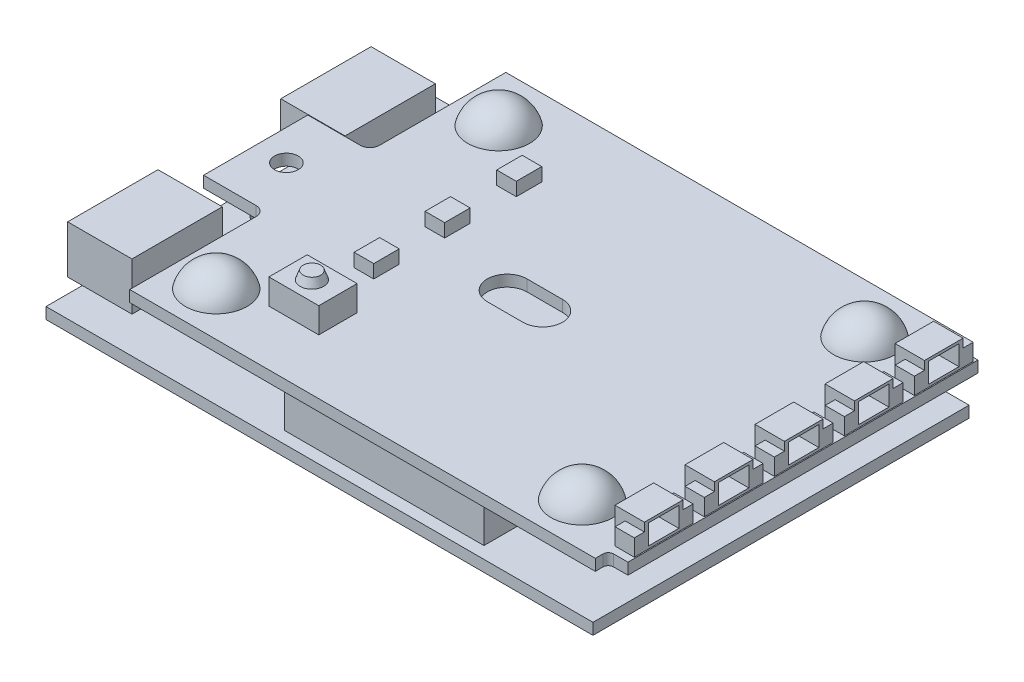
SolidWorks part; units mm, degrees
ref_plane "Front Plane" through (0, 0, 0) normal (0, 0, 1) x (1, 0, 0)
ref_plane "Top Plane" through (0, 0, 0) normal (0, 1, 0) x (1, 0, 0)
ref_plane "Right Plane" through (0, 0, 0) normal (1, 0, 0) x (0, 0, -1)
sketch "Sketch1" plane through (0, 0, 0) normal (0, 1, 0) x (1, 0, 0)
  line L1 (0, 0) -> (77.978, 0)
  line L2 (0, 0) -> (0, -53.6194)
  line L3 (0, -53.6194) -> (77.978, -53.6194)
  line L4 (77.978, 0) -> (77.978, -53.6194)
  dimension "D1" = 77.978
  dimension "D2" = 53.6194
extrude "Bottom Board" add sketch "Sketch1" along normal blind 1.6129
sketch "Sketch2" plane through (0, 1.6129, 0) normal (0, 1, 0) x (-1, 0, 0)
  line L0 (0, 0) -> (0, 53.6194) construction
  line L1 (2.0955, 5.1816) -> (-7.0739, 5.1816)
  line L2 (2.0955, 5.1816) -> (2.0955, 18.0594)
  line L3 (2.0955, 18.0594) -> (-7.0739, 18.0594)
  line L4 (-7.0739, 5.1816) -> (-7.0739, 18.0594)
  line L5 (-77.978, 0) -> (0, 0) construction
  dimension "D1" = 12.8778
  dimension "D2" = 9.1694
  dimension "D3" = 5.1816
  dimension "D4" = 2.0955
extrude "Connector Body" add sketch "Sketch2" along normal blind 6.8199
sketch "Sketch4" plane through (-2.0955, 0, 0) normal (-1, 0, 0) x (0, 0, 1)
  line L0 (5.1816, 8.4328) -> (5.1816, 1.6129) construction
  line L1 (5.7658, 7.8105) -> (8.3947, 7.8105)
  line L2 (5.7658, 7.8105) -> (5.7658, 5.2197)
  line L3 (5.7658, 5.2197) -> (8.3947, 5.2197)
  line L4 (8.3947, 7.8105) -> (8.3947, 5.2197)
  line L5 (5.1816, 8.4328) -> (18.0594, 8.4328) construction
  line L6 (8.7926, 7.8105) -> (8.7926, 5.2197)
  line L7 (8.7926, 5.2197) -> (11.4215, 5.2197)
  line L8 (11.4215, 7.8105) -> (11.4215, 5.2197)
  line L9 (8.7926, 7.8105) -> (11.4215, 7.8105)
  line L10 (11.8195, 7.8105) -> (11.8195, 5.2197)
  line L11 (11.8195, 5.2197) -> (14.4484, 5.2197)
  line L12 (14.4484, 7.8105) -> (14.4484, 5.2197)
  line L13 (11.8195, 7.8105) -> (14.4484, 7.8105)
  line L14 (14.8463, 7.8105) -> (14.8463, 5.2197)
  line L15 (14.8463, 5.2197) -> (17.4752, 5.2197)
  line L16 (17.4752, 7.8105) -> (17.4752, 5.2197)
  line L17 (14.8463, 7.8105) -> (17.4752, 7.8105)
  line L18 (5.7658, 4.826) -> (5.7658, 2.2352)
  line L19 (5.7658, 2.2352) -> (8.3947, 2.2352)
  line L20 (8.3947, 4.826) -> (8.3947, 2.2352)
  line L21 (5.7658, 4.826) -> (8.3947, 4.826)
  line L22 (8.7926, 4.826) -> (8.7926, 2.2352)
  line L23 (8.7926, 2.2352) -> (11.4215, 2.2352)
  line L24 (11.4215, 4.826) -> (11.4215, 2.2352)
  line L25 (8.7926, 4.826) -> (11.4215, 4.826)
  line L26 (11.8195, 4.826) -> (11.8195, 2.2352)
  line L27 (11.8195, 2.2352) -> (14.4484, 2.2352)
  line L28 (14.4484, 4.826) -> (14.4484, 2.2352)
  line L29 (11.8195, 4.826) -> (14.4484, 4.826)
  line L30 (14.8463, 4.826) -> (14.8463, 2.2352)
  line L31 (14.8463, 2.2352) -> (17.4752, 2.2352)
  line L32 (17.4752, 4.826) -> (17.4752, 2.2352)
  line L33 (14.8463, 4.826) -> (17.4752, 4.826)
  line L34 (18.0594, 8.4328) -> (18.0594, 1.6129) construction
  line L35 (17.4752, 7.4085) -> (18.0594, 7.4085) construction
  line L36 (5.7658, 7.5345) -> (5.1816, 7.5345) construction
  line L37 (7.8077, 7.8105) -> (7.8077, 8.4328)
  line L38 (7.8077, 2.2352) -> (7.8077, 1.6129)
  line L39 (5.1816, 1.6129) -> (18.0594, 1.6129) construction
  dimension "D1" = 2.6289
  dimension "D2" = 2.5908
  dimension "D3" = 0.5842
  dimension "D4" = 0.6223
  dimension "D5" = 4
  dimension "D6" = 2
extrude "Connector Holes" cut sketch "Sketch4" against normal blind 5.08 contours L4 L1 L2 L3 | L9 L6 L7 L8 | L13 L10 L11 L12 | L17 L14 L15 L16 | L33 L30 L31 L32 | L29 L26 L27 L28 | L25 L22 L23 L24 | L21 L18 L19 L20 region at (-2.0955, 6.5151, 7.0802) region at (-2.0955, 6.5151, 10.1071) region at (-2.0955, 6.5151, 13.1339) region at (-2.0955, 6.5151, 16.1608) region at (-2.0955, 3.5306, 7.0802) region at (-2.0955, 3.5306, 10.1071) region at (-2.0955, 3.5306, 13.1339) region at (-2.0955, 3.5306, 16.1608)
ref_plane "Center Plane" through (0, 0, 26.8097) normal (0, 0, -1) x (-1, 0, 0)
mirror "Connector Mirror" about plane through (0, 0, 26.8097) normal (0, 0, -1) of "Connector Holes", "Connector Body"
sketch "Sketch5" plane through (0, 1.6129, 0) normal (0, 1, 0) x (1, 0, 0)
  line L0 (77.978, -26.8097) -> (0, -26.8097) construction
  line L1 (77.978, -53.6194) -> (77.978, 0) construction
  line L2 (0, -18.0594) -> (0, -35.56) construction
  line L3 (2.9845, -26.8097) -> (2.9845, -21.4955) construction
  line L4 (36.0172, -26.8097) -> (36.0172, -8.1241) construction
  line L5 (0, -18.0594) -> (0, -35.56) construction
  circle A0 centre (4.68, -26.8097) radius 1.6955
  circle A1 centre (39.0652, -26.8097) radius 3.048
  dimension "D1" = 3.3909
  dimension "D3" = 6.096
  dimension "D2" = 2.9845
  dimension "D4" = 36.0172
extrude "Bottom Board Hole" cut sketch "Sketch5" against normal up to next
sketch "Sketch6" plane through (0, 1.6129, 0) normal (0, 1, 0) x (-1, 0, 0)
  line L0 (-77.978, 0) -> (0, 0) construction
  line L1 (-39.37, 1.7018) -> (-67.818, 1.7018)
  line L2 (-39.37, 1.7018) -> (-39.37, 7.2644)
  line L3 (-39.37, 7.2644) -> (-67.818, 7.2644)
  line L4 (-67.818, 1.7018) -> (-67.818, 7.2644)
  line L5 (-77.978, 53.6194) -> (-77.978, 0) construction
  line L6 (-32.2834, 46.355) -> (-60.7314, 46.355)
  line L7 (-32.2834, 46.355) -> (-32.2834, 51.9176)
  line L8 (-32.2834, 51.9176) -> (-60.7314, 51.9176)
  line L9 (-60.7314, 46.355) -> (-60.7314, 51.9176)
  line L10 (0, 18.0594) -> (0, 35.56) construction
  line L12 (-44.4047, 1.7018) -> (-44.4047, 0) construction
  line L13 (-37.561, 51.9176) -> (-37.561, 53.6194) construction
  line L14 (0, 53.6194) -> (-77.978, 53.6194) construction
  dimension "D1" = 28.448
  dimension "D2" = 5.5626
  dimension "D3" = 1.7018
  dimension "D4" = 10.16
  dimension "D5" = 28.448
  dimension "D6" = 5.5626
  dimension "D7" = 32.2834
extrude "Layer Connectors" add sketch "Sketch6" along normal blind 6.4516
sketch "Sketch7" plane through (0, 8.0645, 0) normal (0, 1, 0) x (1, 0, 0)
  line L0 (77.978, -53.6194) -> (77.978, 0) construction
  line L1 (78.3082, 0) -> (11.938, 0)
  line L2 (81.1022, -1.8542) -> (81.1022, -51.7652)
  line L3 (78.3082, -53.6194) -> (11.938, -53.6194)
  line L4 (11.938, 0) -> (11.938, -18.0086)
  line L5 (0, -18.0594) -> (0, -35.56) construction
  line L6 (77.978, 0) -> (0, 0) construction
  line L7 (0, -53.6194) -> (77.978, -53.6194) construction
  line L8 (15.6034, 0) -> (15.6034, -19.3802) construction
  line L9 (10.5664, -19.3802) -> (3.0861, -19.3802)
  line L10 (11.938, -35.6108) -> (11.938, -53.6194)
  line L11 (10.5664, -34.2392) -> (3.0861, -34.2392)
  line L12 (3.0861, -19.3802) -> (3.0861, -34.2392)
  line L13 (10.5664, -19.3802) -> (15.6034, -19.3802) construction
  line L14 (16.8171, -34.2392) -> (16.8171, -53.6194) construction
  line L15 (10.5664, -34.2392) -> (16.8171, -34.2392) construction
  line L16 (77.978, -26.8097) -> (0, -26.8097) construction
  line L17 (5.7658, -26.8097) -> (5.7658, -22.9762) construction
  line L18 (36.1061, -26.8097) -> (46.8249, -26.8097) construction
  line L19 (38.9318, -23.984) -> (43.9992, -23.984)
  line L20 (36.1061, -26.8097) -> (36.1061, -33.1542) construction
  line L21 (38.9318, -29.6354) -> (43.9992, -29.6355)
  line L22 (78.3082, -53.6194) -> (78.3082, -52.5272)
  line L23 (81.1022, -51.7652) -> (79.0702, -51.7652)
  line L25 (81.1022, -1.8542) -> (79.0702, -1.8542)
  line L26 (78.3082, 0) -> (78.3082, -1.0922)
  arc A0 (11.938, -18.0086) -> (10.5664, -19.3802) centre (10.5664, -18.0086) cw
  arc A1 (10.5664, -34.2392) -> (11.938, -35.6108) centre (10.5664, -35.6108) cw
  circle A2 centre (7.4613, -26.8097) radius 1.6955
  circle A3 centre (4.68, -26.8097) radius 1.6955 construction
  arc A4 (38.9318, -29.6354) -> (38.9318, -23.984) centre (38.9318, -26.8097) cw
  arc A5 (43.9992, -23.984) -> (43.9992, -29.6355) centre (43.9992, -26.8097) cw
  arc A6 (79.0702, -1.8542) -> (78.3082, -1.0922) centre (79.0702, -1.0922) cw
  arc A7 (79.0702, -51.7652) -> (78.3082, -52.5272) centre (79.0702, -52.5272) ccw
  point P45 (78.3082, -1.8542)
  dimension "D5" = 1.3716
  dimension "D6" = 1.3716
  dimension "D13" = 0.762
  dimension "D1" = 3.1242
  dimension "D2" = 11.938
  dimension "D3" = 19.3802
  dimension "D4" = 3.0861
  dimension "D7" = 2.6797
  dimension "D8" = 5.6515
  dimension "D9" = 10.7188
  dimension "D10" = 33.02
  dimension "D11" = 2.794
  dimension "D12" = 1.8542
extrude "Top Board" add sketch "Sketch7" along normal blind 1.6129
sketch "Sketch8" plane through (0, 9.6774, 0) normal (0, 1, 0) x (1, 0, 0)
  line L1 (80.9498, -2.3876) -> (78.2066, -2.3876)
  line L2 (80.9498, -2.3876) -> (80.9498, -10.7696)
  line L3 (80.9498, -10.7696) -> (78.2066, -10.7696)
  line L4 (78.2066, -2.3876) -> (78.2066, -10.7696)
  line L5 (78.3082, 0) -> (11.938, 0) construction
  line L6 (81.1022, -51.7652) -> (81.1022, -1.8542) construction
  dimension "D1" = 2.7432
  dimension "D2" = 8.382
  dimension "D3" = 2.3876
  dimension "D4" = 0.1524
extrude "Maker Connector Sides" add sketch "Sketch8" along normal blind 2.3876
sketch "Sketch9" plane through (0, 12.065, 0) normal (0, 1, 0) x (1, 0, 0)
  line L0 (80.9498, -10.7696) -> (80.9498, -2.3876) construction
  line L1 (80.9498, -3.8227) -> (76.7588, -3.8227)
  line L2 (80.9498, -3.8227) -> (80.9498, -9.3345)
  line L3 (80.9498, -9.3345) -> (76.7588, -9.3345)
  line L4 (76.7588, -3.8227) -> (76.7588, -9.3345)
  line L6 (78.7411, -2.3876) -> (78.7411, -3.8227) construction
  line L7 (80.9498, -2.3876) -> (78.2066, -2.3876) construction
  line L9 (78.7411, -9.3345) -> (78.7411, -10.7696) construction
  line L10 (78.2066, -10.7696) -> (80.9498, -10.7696) construction
  dimension "D1" = 5.5118
  dimension "D2" = 4.191
extrude "Marker Connector Box" add sketch "Sketch9" along normal blind 1.2192
sketch "Sketch10" plane through (0, 9.6774, 0) normal (0, 1, 0) x (1, 0, 0)
  line L0 (76.7588, -9.3345) -> (78.2066, -9.3345) construction
  line L1 (78.2066, -3.8227) -> (76.7588, -3.8227) construction
  line L2 (76.7588, -3.8227) -> (76.7588, -9.3345) construction
  line L3 (76.7588, -9.3345) -> (78.2066, -9.3345)
  line L4 (78.2066, -3.8227) -> (76.7588, -3.8227)
  line L5 (76.7588, -3.8227) -> (76.7588, -9.3345)
  line L10 (78.2066, -3.8227) -> (76.7588, -3.8227)
  line L11 (78.2066, -9.3345) -> (78.2066, -3.8227)
  line L12 (76.7588, -9.3345) -> (78.2066, -9.3345)
  line L13 (76.7588, -3.8227) -> (76.7588, -9.3345)
  line L14 (78.2066, -3.8227) -> (76.7588, -3.8227)
  line L15 (78.2066, -9.3345) -> (78.2066, -3.8227)
  line L16 (76.7588, -9.3345) -> (78.2066, -9.3345)
  line L17 (76.7588, -3.8227) -> (76.7588, -9.3345)
  line M11 (78.2066, -10.7696) -> (78.2066, -2.3876)
  dimension "D1" = 0
extrude "Marker Connector Rear" add sketch "Sketch10" along normal up to body contours L4 L5 L3 M11 region at (77.4827, 9.6774, 6.5786)
sketch "Sketch11" plane through (81.1022, 0, 0) normal (1, 0, 0) x (0, 0, -1)
  line L0 (-9.3345, 13.2842) -> (-9.3345, 12.065) construction
  line L1 (-8.7376, 12.9032) -> (-4.4196, 12.9032)
  line L2 (-8.7376, 12.9032) -> (-8.7376, 10.0584)
  line L3 (-8.7376, 10.0584) -> (-4.4196, 10.0584)
  line L4 (-4.4196, 12.9032) -> (-4.4196, 10.0584)
  line L5 (-8.7376, 11.497) -> (-9.3345, 11.497) construction
  line L6 (-4.4196, 12.3526) -> (-3.8227, 12.3526) construction
  line L7 (-3.8227, 13.2842) -> (-3.8227, 12.065) construction
  line L8 (-9.3345, 13.2842) -> (-3.8227, 13.2842) construction
  line L10 (-7.3098, 10.0584) -> (-7.3098, 9.6774) construction
  line L11 (-51.7652, 9.6774) -> (-1.8542, 9.6774) construction
  line L12 (-7.3098, 13.2842) -> (-7.3098, 12.9032) construction
  dimension "D1" = 0.5969
  dimension "D2" = 0.381
extrude "Marker Connector " cut sketch "Sketch11" against normal blind 3.175
pattern_linear "Maker Connectors Pattern" count 5 spacing 9.9822 along (0, 0, 1) of "Marker Connector Box", "Marker Connector ", "Maker Connector Sides", "Marker Connector Rear"
sketch "Sketch12" plane through (0, 9.6774, 0) normal (0, 1, 0) x (-1, 0, 0)
  line L0 (-13.589, 7.0866) -> (-13.589, -6.6902) construction
  line L1 (-11.938, 0) -> (-11.938, 18.0086) construction
  line L2 (-17.9959, 2.6797) -> (-29.745, 2.6797) construction
  line L3 (-78.3082, 0) -> (-11.938, 0) construction
  circle A0 centre (-17.9959, 7.0866) radius 4.4069
  dimension "D1" = 8.8138
  dimension "D2" = 1.651
  dimension "D3" = 2.6797
extrude "Glue Dome" add sketch "Sketch12" along normal blind 3.4036
fillet "Glue Dome Fillet" radius 4.5415 1 edges at (17.9959, 13.081, 11.4935)
pattern_linear "Glue pattern" count 2 spacing 40.259 along (0, 0, 1) count 2 spacing 52.1462 along (1, 0, 0) of "Glue Dome Fillet", "Glue Dome"
sketch "Sketch13" plane through (0, 9.6774, 0) normal (0, 1, 0) x (-1, 0, 0)
  line L0 (-78.3082, 0) -> (-11.938, 0) construction
  line L1 (-25.2349, 10.9728) -> (-28.0289, 10.9728)
  line L2 (-25.2349, 10.9728) -> (-25.2349, 14.605)
  line L3 (-25.2349, 14.605) -> (-28.0289, 14.605)
  line L4 (-28.0289, 10.9728) -> (-28.0289, 14.605)
  line L5 (-3.0861, 19.3802) -> (-3.0861, 34.2392) construction
  line L7 (-25.2349, 21.1836) -> (-28.0289, 21.1836)
  line L8 (-25.2349, 21.1836) -> (-25.2349, 24.8158)
  line L9 (-25.2349, 24.8158) -> (-28.0289, 24.8158)
  line L10 (-28.0289, 21.1836) -> (-28.0289, 24.8158)
  line L11 (-25.2349, 31.2928) -> (-28.0289, 31.2928)
  line L12 (-25.2349, 31.2928) -> (-25.2349, 34.925)
  line L13 (-25.2349, 34.925) -> (-28.0289, 34.925)
  line L14 (-28.0289, 31.2928) -> (-28.0289, 34.925)
  dimension "D1" = 2.794
  dimension "D2" = 3.6322
  dimension "D3" = 10.9728
  dimension "D4" = 22.1488
  dimension "D5" = 24.8158
  dimension "D6" = 34.925
extrude "LEDs" add sketch "Sketch13" along normal blind 1.905
sketch "Sketch14" plane through (0, 9.6774, 0) normal (0, 1, 0) x (-1, 0, 0)
  line L0 (-11.938, 53.6194) -> (-78.3082, 53.6194) construction
  line L1 (-23.9014, 40.2844) -> (-31.0134, 40.2844)
  line L2 (-23.9014, 40.2844) -> (-23.9014, 45.7454)
  line L3 (-23.9014, 45.7454) -> (-31.0134, 45.7454)
  line L4 (-31.0134, 40.2844) -> (-31.0134, 45.7454)
  line L5 (-81.1022, 51.7652) -> (-81.1022, 1.8542) construction
  dimension "D1" = 7.112
  dimension "D2" = 5.461
  dimension "D3" = 7.874
  dimension "D4" = 50.0888
extrude "IR receiver base" add sketch "Sketch14" along normal blind 3.6068
sketch "Sketch16" plane through (0, 13.2842, 0) normal (0, 1, 0) x (-1, 0, 0)
  line L0 (-27.305, 40.2844) -> (-27.305, 45.7454) construction
  line L3 (-31.0134, 40.2844) -> (-23.9014, 40.2844) construction
  line L4 (-23.9014, 45.7454) -> (-31.0134, 45.7454) construction
  line L5 (-28.9814, 43.0149) -> (-28.9814, 38.6964) construction
  line L6 (-23.9014, 40.2844) -> (-23.9014, 45.7454) construction
  circle A0 centre (-27.305, 43.0149) radius 1.6764
  circle A1 centre (-27.305, 43.0149) radius 1.2446 construction
  dimension "D1" = 3.3528
  dimension "D2" = 2.4892
  dimension "D3" = 5.08
ref_plane "Plane for IR receiver" through (0, 14.4526, 0) normal (0, 1, 0) x (-1, 0, 0)
sketch "Sketch17" plane through (0, 14.4526, 0) normal (0, 1, 0) x (-1, 0, 0)
  circle A0 centre (-27.305, 43.0149) radius 1.2446 construction
  circle A3 centre (-27.305, 43.0149) radius 1.2446
loft "IR receiver" add profiles "Sketch16", "Sketch17" connector at (28.1584, 13.2842, 44.4578) connector at (27.9456, 14.4526, 44.082)
sketch "Sketch18" plane through (0, 0, 0) normal (0, -1, 0) x (1, 0, 0)
  line L0 (0, 53.6194) -> (77.978, 53.6194) construction
  line L1 (15.2908, 49.5554) -> (18.0848, 49.5554)
  line L2 (15.2908, 49.5554) -> (15.2908, 44.5262)
  line L3 (15.2908, 44.5262) -> (18.0848, 44.5262)
  line L4 (18.0848, 49.5554) -> (18.0848, 44.5262)
  line L5 (0, 0) -> (0, 53.6194) construction
  line L6 (15.2908, 42.7228) -> (18.0848, 42.7228)
  line L7 (15.2908, 42.7228) -> (15.2908, 37.6936)
  line L8 (15.2908, 37.6936) -> (18.0848, 37.6936)
  line L9 (18.0848, 42.7228) -> (18.0848, 37.6936)
  line L10 (77.978, 0) -> (0, 0) construction
  line L11 (20.32, 36.0934) -> (23.114, 36.0934)
  line L12 (20.32, 36.0934) -> (20.32, 31.0642)
  line L13 (20.32, 31.0642) -> (23.114, 31.0642)
  line L14 (23.114, 36.0934) -> (23.114, 31.0642)
  dimension "D1" = 2.794
  dimension "D2" = 5.0292
  dimension "D3" = 4.064
  dimension "D4" = 15.2908
  dimension "D5" = 2.794
  dimension "D6" = 5.0292
  dimension "D7" = 37.6936
  dimension "D8" = 2.794
  dimension "D9" = 5.0292
  dimension "D10" = 20.32
  dimension "D11" = 17.526
extrude "Back components" add sketch "Sketch18" along normal blind 2.4892
sketch "Sketch19" plane through (0, 0, 0) normal (0, -1, 0) x (1, 0, 0)
  line L0 (0, 53.6194) -> (77.978, 53.6194) construction
  line L1 (36.3093, 43.5864) -> (38.0873, 43.5864)
  line L2 (36.3093, 43.5864) -> (36.3093, 40.513)
  line L3 (36.3093, 40.513) -> (38.0873, 40.513)
  line L4 (38.0873, 43.5864) -> (38.0873, 40.513)
  line L5 (77.978, 53.6194) -> (77.978, 0) construction
  line L6 (40.3606, 37.338) -> (42.1386, 37.338)
  line L7 (40.3606, 37.338) -> (40.3606, 34.2646)
  line L8 (40.3606, 34.2646) -> (42.1386, 34.2646)
  line L9 (42.1386, 37.338) -> (42.1386, 34.2646)
  line L10 (51.3334, 18.923) -> (53.1114, 18.923)
  line L11 (51.3334, 18.923) -> (51.3334, 15.8496)
  line L12 (51.3334, 15.8496) -> (53.1114, 15.8496)
  line L13 (53.1114, 18.923) -> (53.1114, 15.8496)
  line L14 (77.978, 0) -> (0, 0) construction
  line L15 (34.9758, 15.24) -> (36.7538, 15.24)
  line L16 (34.9758, 15.24) -> (34.9758, 12.1666)
  line L17 (34.9758, 12.1666) -> (36.7538, 12.1666)
  line L18 (36.7538, 15.24) -> (36.7538, 12.1666)
  line L19 (41.3004, 15.24) -> (43.0784, 15.24)
  line L20 (41.3004, 15.24) -> (41.3004, 12.1666)
  line L21 (41.3004, 12.1666) -> (43.0784, 12.1666)
  line L22 (43.0784, 15.24) -> (43.0784, 12.1666)
  line L23 (74.295, 50.7619) -> (76.073, 50.7619)
  line L24 (74.295, 50.7619) -> (74.295, 47.6885)
  line L25 (74.295, 47.6885) -> (76.073, 47.6885)
  line L26 (76.073, 50.7619) -> (76.073, 47.6885)
  line L27 (70.231, 10.287) -> (70.231, 12.065)
  line L28 (70.231, 10.287) -> (73.3044, 10.287)
  line L29 (73.3044, 10.287) -> (73.3044, 12.065)
  line L30 (70.231, 12.065) -> (73.3044, 12.065)
  line L31 (70.231, 6.2484) -> (70.231, 8.0264)
  line L32 (70.231, 6.2484) -> (73.3044, 6.2484)
  line L33 (73.3044, 6.2484) -> (73.3044, 8.0264)
  line L34 (70.231, 8.0264) -> (73.3044, 8.0264)
  line L35 (23.4315, 27.3558) -> (25.2095, 27.3558)
  line L36 (23.4315, 27.3558) -> (23.4315, 24.2824)
  line L37 (23.4315, 24.2824) -> (25.2095, 24.2824)
  line L38 (25.2095, 27.3558) -> (25.2095, 24.2824)
  line L39 (16.9799, 12.0904) -> (18.7579, 12.0904)
  line L40 (16.9799, 12.0904) -> (16.9799, 9.017)
  line L41 (16.9799, 9.017) -> (18.7579, 9.017)
  line L42 (18.7579, 12.0904) -> (18.7579, 9.017)
  line L43 (0, 0) -> (0, 53.6194) construction
  dimension "D1" = 1.778
  dimension "D2" = 3.0734
  dimension "D3" = 10.033
  dimension "D4" = 39.8907
  dimension "D5" = 1.778
  dimension "D6" = 16.2814
  dimension "D7" = 35.8394
  dimension "D8" = 18.923
  dimension "D9" = 26.6446
  dimension "D10" = 43.0022
  dimension "D11" = 15.24
  dimension "D12" = 36.6776
  dimension "D13" = 5.9309
  dimension "D14" = 3.683
  dimension "D15" = 12.065
  dimension "D16" = 7.747
  dimension "D17" = 8.0264
  dimension "D18" = 27.3558
  dimension "D19" = 25.2095
  dimension "D20" = 18.7579
  dimension "D21" = 12.0904
extrude "Bottom caps" add sketch "Sketch19" along normal blind 1.7526
sketch "Sketch20" plane through (0, 0, 0) normal (0, -1, 0) x (1, 0, 0)
  line L0 (77.978, 0) -> (0, 0) construction
  line L1 (26.924, 6.477) -> (31.8516, 6.477)
  line L2 (26.924, 6.477) -> (26.924, 2.6162)
  line L3 (26.924, 2.6162) -> (31.8516, 2.6162)
  line L4 (31.8516, 6.477) -> (31.8516, 2.6162)
  line L5 (0, 0) -> (0, 53.6194) construction
  dimension "D1" = 4.9276
  dimension "D2" = 3.8608
  dimension "D3" = 6.477
  dimension "D4" = 31.8516
extrude "Chip" add sketch "Sketch20" along normal blind 1.5875
sketch "Sketch21" plane through (0, 0, 0) normal (0, -1, 0) x (1, 0, 0)
  line L0 (77.978, 0) -> (0, 0) construction
  line L1 (54.102, 12.0777) -> (55.5498, 12.0777)
  line L2 (54.102, 12.0777) -> (54.102, 10.0203)
  line L3 (54.102, 10.0203) -> (55.5498, 10.0203)
  line L4 (55.5498, 12.0777) -> (55.5498, 10.0203)
  line L5 (77.978, 53.6194) -> (77.978, 0) construction
  line L6 (57.3278, 12.0777) -> (58.7756, 12.0777)
  line L7 (57.3278, 12.0777) -> (57.3278, 10.0203)
  line L8 (57.3278, 10.0203) -> (58.7756, 10.0203)
  line L9 (58.7756, 12.0777) -> (58.7756, 10.0203)
  line L10 (29.6926, 49.5808) -> (29.6926, 51.0286)
  line L11 (29.6926, 49.5808) -> (31.75, 49.5808)
  line L12 (31.75, 49.5808) -> (31.75, 51.0286)
  line L13 (29.6926, 51.0286) -> (31.75, 51.0286)
  line L14 (0, 53.6194) -> (77.978, 53.6194) construction
  line L15 (0, 0) -> (0, 53.6194) construction
  dimension "D1" = 1.4478
  dimension "D2" = 2.0574
  dimension "D3" = 12.0777
  dimension "D4" = 23.876
  dimension "D5" = 20.6502
  dimension "D6" = 4.0386
  dimension "D7" = 31.75
extrude "FLs" add sketch "Sketch21" along normal blind 0.9779
sketch "Sketch22" plane through (0, 0, 0) normal (0, -1, 0) x (1, 0, 0)
  line L0 (77.978, 53.6194) -> (77.978, 0) construction
  line L1 (59.69, 34.4043) -> (74.9173, 34.4043)
  line L2 (59.69, 34.4043) -> (59.69, 19.177)
  line L3 (59.69, 19.177) -> (74.9173, 19.177)
  line L4 (74.9173, 34.4043) -> (74.9173, 19.177)
  line L5 (0, 53.6194) -> (77.978, 53.6194) construction
  dimension "D1" = 15.2273
  dimension "D2" = 18.288
  dimension "D3" = 34.4424
extrude "Xilinx" add sketch "Sketch22" along normal blind 1.0922
sketch "Sketch23" plane through (0, 0, 0) normal (0, -1, 0) x (1, 0, 0)
  line L0 (0, 53.6194) -> (77.978, 53.6194) construction
  line L1 (19.6215, 43.6626) -> (21.0312, 43.6626)
  line L2 (19.6215, 43.6626) -> (19.6215, 41.5036)
  line L3 (19.6215, 41.5036) -> (21.0312, 41.5036)
  line L4 (21.0312, 43.6626) -> (21.0312, 41.5036)
  line L5 (77.978, 53.6194) -> (77.978, 0) construction
  line L6 (23.5839, 43.7134) -> (24.9936, 43.7134)
  line L7 (23.5839, 43.7134) -> (23.5839, 41.5544)
  line L8 (23.5839, 41.5544) -> (24.9936, 41.5544)
  line L9 (24.9936, 43.7134) -> (24.9936, 41.5544)
  line L10 (23.5839, 47.5996) -> (24.9936, 47.5996)
  line L11 (23.5839, 47.5996) -> (23.5839, 45.4406)
  line L12 (23.5839, 45.4406) -> (24.9936, 45.4406)
  line L13 (24.9936, 47.5996) -> (24.9936, 45.4406)
  line L14 (0, 0) -> (0, 53.6194) construction
  line L15 (30.4038, 40.005) -> (31.8135, 40.005)
  line L16 (30.4038, 40.005) -> (30.4038, 37.846)
  line L17 (30.4038, 37.846) -> (31.8135, 37.846)
  line L18 (31.8135, 40.005) -> (31.8135, 37.846)
  dimension "D1" = 1.4097
  dimension "D2" = 2.159
  dimension "D3" = 12.1158
  dimension "D4" = 58.3565
  dimension "D5" = 12.065
  dimension "D6" = 8.1788
  dimension "D7" = 24.9936
  dimension "D8" = 15.7734
  dimension "D9" = 47.5742
extrude "Cs" add sketch "Sketch23" along normal blind 1.5494
